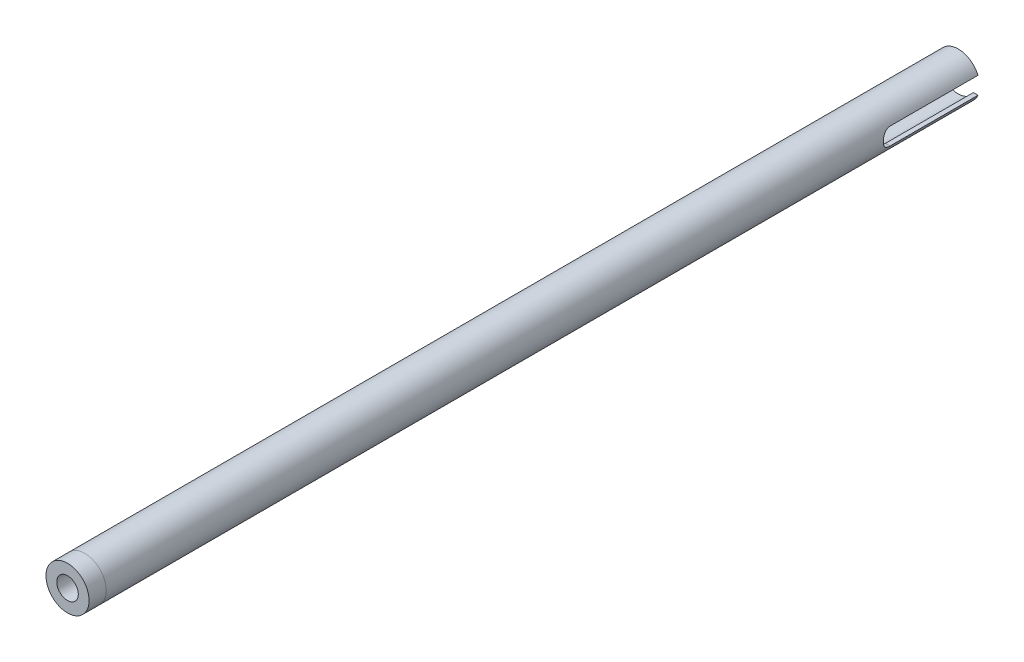
SolidWorks part; units mm, degrees
material "AISI 4130 Steel, annealed at 865C"
ref_plane "Front Plane" through (0, 0, 0) normal (0, 0, 1) x (1, 0, 0)
ref_plane "Top Plane" through (0, 0, 0) normal (0, 1, 0) x (1, 0, 0)
ref_plane "Right Plane" through (0, 0, 0) normal (1, 0, 0) x (0, 0, -1)
sketch "Axis" plane through (0, 0, 0) normal (0, 1, 0) x (1, 0, 0)
  line L0 (0, 0) -> (0, 328.0702) construction
  line L1 (0, 0) -> (0, -28.575) construction
  line L2 (0, 328.0702) -> (-7.9375, 328.0702) construction
  line L4 (0, 356.4735) -> (-26.4371, 261.8721) construction
  dimension "D1" = 28.575
  dimension "D2" = 7.9375
sketch "Sketch1" plane through (0, 0, 0) normal (0, 0, 1) x (1, 0, 0)
  line L0 (-7.9375, 0) -> (7.9375, 0) construction
  line L1 (-7.2748, 3.175) -> (7.2748, 3.175)
  line L2 (-7.2748, -3.175) -> (7.2748, -3.175)
  circle A0 centre (0, 0) radius 7.9375
  circle A1 centre (0, 0) radius 6.4135
  circle A2 centre (0, 0) radius 3.9688
  dimension "D1" = 15.875
  dimension "D3" = 7.9375
  dimension "D2" = 1.524
  dimension "D4" = 6.35
extrude "Threaded insert 1-1" add sketch "Sketch1" against normal blind 6.35 contours A2 L1 A1 | A1 L1 A0 | A2 L0 A1 L1 | A1 L0 A0 L1 | L0 A1 L2 A0 | L0 A2 L2 A1 | A2 L2 A1 | A1 L2 A0 | L0 A1 L2 A2 | L0 A0 L2 A1 | A0 L0 A1 L1 | A1 L0 A2 L1 region at (4.7887, 1.6543, 0) region at (4.7887, -1.6543, 0) region at (6.9234, 1.6163, 0) region at (6.9234, -1.6163, 0) region at (-4.7887, -1.6543, 0) region at (-4.7887, 1.6543, 0) region at (0, 4.6159, 0) region at (0, -4.6159, 0) region at (0, 6.5666, 0) region at (6.4237, -3.3281, 0) region at (-6.9234, -1.6163, 0) region at (-6.9234, 1.6163, 0)
extrude "Threaded insert 1-2" add sketch "Sketch1<3>" against normal blind 9.525 from surface contours A2 L1 A1 | A2 L0 A1 L1 | L0 A2 L2 A1 | A2 L2 A1 | L0 A1 L2 A2 | A1 L0 A2 L1 region at (4.7887, 1.6543, 0) region at (4.7887, -1.6543, 0) region at (-4.7887, -1.6543, 0) region at (-4.7887, 1.6543, 0) region at (0, 4.6159, 0) region at (0, -4.6159, 0) starting at face at (7.9375, 0, -6.35)
sketch "Sketch1<3>" plane through (0, 0, 0) normal (0, 0, 1) x (1, 0, 0) same geometry as "Sketch1"
extrude "A-arm tube" add sketch "Sketch1<4>" against normal up to vertex (328.0702 mm away) from surface separate body contours A1 L1 A0 | A1 L0 A0 L1 | L0 A1 L2 A0 | A1 L2 A0 | L0 A0 L2 A1 | A0 L0 A1 L1 region at (6.9234, 1.6163, 0) region at (6.9234, -1.6163, 0) region at (0, 6.5666, 0) region at (6.4237, -3.3281, 0) region at (-6.9234, -1.6163, 0) region at (-6.9234, 1.6163, 0) up to point (0, 0, -328.0702) starting at face at (6.4135, 0, -6.35)
sketch "Sketch1<4>" plane through (0, 0, 0) normal (0, 0, 1) x (1, 0, 0) same geometry as "Sketch1"
extrude "Apex slot" cut sketch "Sketch1<5>" along normal blind 35.56 from surface contours A0 L0 A1 L1 | L0 A0 L2 A1 | A1 L0 A0 L1 | L0 A1 L2 A0 region at (6.9234, 1.6163, 0) region at (6.9234, -1.6163, 0) region at (-6.9234, -1.6163, 0) region at (-6.9234, 1.6163, 0) starting at face at (6.4135, 0, -328.0702)
sketch "Sketch1<5>" plane through (0, 0, 0) normal (0, 0, 1) x (1, 0, 0) same geometry as "Sketch1"
fillet "Fillet1" radius 3.175 4 edges at (-6.4237, 3.175, -292.5102) (-6.4237, -3.175, -292.5102) (6.4237, -3.175, -292.5102) (6.4237, 3.175, -292.5102)
equation "\"tube diameter\"= 5 / 8"
equation "\"tube thickness\"= .06"
equation "\"apex thickness\"= .25"
equation "\"tube slot\"= 1.4"
equation "\"D1@Sketch1\"=\"tube diameter\""
equation "\"D2@Sketch1\"=\"tube thickness\""
equation "\"threaded insert hole\"= .3125"
equation "\"D3@Sketch1\"=\"threaded insert hole\""
equation "\"D4@Sketch1\"=\"apex thickness\""
equation "\"D1@Apex slot\" = \"tube slot\""
equation "\"D1@Fillet1\"=\"apex thickness\"/2"
equation "\"D2@Axis\"=\"tube diameter\"/2"
